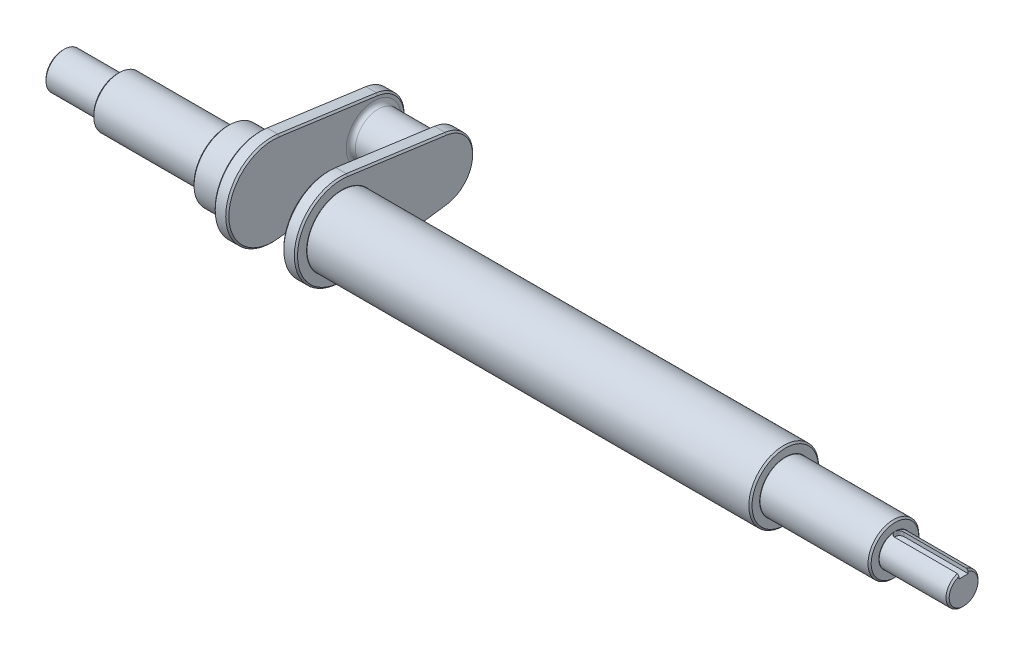
SolidWorks part; units mm, degrees
material "AISI 347 Annealed Stainless Steel (SS)"
ref_plane "Front Plane" through (0, 0, 0) normal (0, 0, 1) x (1, 0, 0)
ref_plane "Top Plane" through (0, 0, 0) normal (0, 1, 0) x (1, 0, 0)
ref_plane "Right Plane" through (0, 0, 0) normal (1, 0, 0) x (0, 0, -1)
ref_plane "R-JPlane" through (30, 0, 0) normal (1, 0, 0) x (0, 0, -1)
ref_plane "L-JPlane" through (-30, 0, 0) normal (1, 0, 0) x (0, 0, -1)
sketch "Sketch1" plane through (-30, 0, 0) normal (1, 0, 0) x (0, 0, -1)
  circle A0 centre (0, 0) radius 38.1
  dimension "D1" = 76.2
extrude "Left-Shaft" add sketch "Sketch1" against normal blind 50
sketch "Sketch2" plane through (30, 0, 0) normal (1, 0, 0) x (0, 0, -1)
  circle A0 centre (0, 0) radius 38.1
  dimension "D1" = 76.2
extrude "Right-Shaft" add sketch "Sketch2" along normal blind 500 separate body
sketch "Sketch5" plane through (-30, 0, 0) normal (1, 0, 0) x (0, 0, -1)
  line L0 (6.8182, 49.5329) -> (114.7727, 34.6731)
  line L1 (6.8182, -49.5329) -> (114.7727, -34.6731)
  arc A0 (6.8182, 49.5329) -> (6.8182, -49.5329) centre (0, 0) ccw
  arc A1 (114.7727, -34.6731) -> (114.7727, 34.6731) centre (110, 0) ccw
  dimension "D1" = 100
  dimension "D2" = 70
  dimension "D3" = 110
extrude "L-Crank" add sketch "Sketch5" against normal blind 15
sketch "Sketch6" plane through (30, 0, 0) normal (1, 0, 0) x (0, 0, -1)
  line L2 (114.7727, 34.6731) -> (6.8182, 49.5329)
  line L3 (6.8182, -49.5329) -> (114.7727, -34.6731)
  line L4 (114.7727, 34.6731) -> (6.8182, 49.5329)
  line L5 (6.8182, -49.5329) -> (114.7727, -34.6731)
  arc A2 (114.7727, -34.6731) -> (114.7727, 34.6731) centre (110, 0) ccw
  arc A3 (6.8182, 49.5329) -> (6.8182, -49.5329) centre (0, 0) ccw
  arc A4 (114.7727, -34.6731) -> (114.7727, 34.6731) centre (110, 0) ccw
  arc A5 (6.8182, 49.5329) -> (6.8182, -49.5329) centre (0, 0) ccw
  dimension "D1" = 0
extrude "R-Crank" add sketch "Sketch6" along normal blind 15
sketch "Sketch7" plane through (-30, 0, 0) normal (1, 0, 0) x (0, 0, -1)
  circle A0 centre (110, 0) radius 25
  dimension "D1" = 50
extrude "Crank Bearing" add sketch "Sketch7" along direction (1, 0, 0) on the side of the normal up to next (60 mm away)
sketch "Sketch3" plane through (-80, 0, 0) normal (-1, 0, 0) x (0, 0, 1)
  circle A0 centre (0, 0) radius 27.7813
  dimension "D1" = 55.5625
extrude "L_Journal" add sketch "Sketch3" along normal blind 120
sketch "Sketch8" plane through (530, 0, 0) normal (1, 0, 0) x (0, 0, -1)
  circle A0 centre (0, 0) radius 27.7813
  dimension "D1" = 55.5625
extrude "R_Journal" add sketch "Sketch8" along normal blind 120
sketch "Sketch9" plane through (-200, 0, 0) normal (-1, 0, 0) x (0, 0, 1)
  circle A0 centre (0, 0) radius 20
  dimension "D1" = 40
extrude "FlyWheel Shaft" add sketch "Sketch9" along normal blind 60
sketch "Sketch10" plane through (650, 0, 0) normal (1, 0, 0) x (0, 0, -1)
  circle A0 centre (0, 0) radius 17.5
  dimension "D1" = 35
extrude "Gear Shaft" add sketch "Sketch10" along normal blind 75
ref_plane "Keyway PLANE" through (0, 12.5, 0) normal (0, 1, 0) x (1, 0, 0)
sketch "Sketch11" plane through (0, 12.5, 0) normal (0, 1, 0) x (1, 0, 0)
  line L0 (745, 0) -> (655, 0) construction
  line L1 (745, -5) -> (655, -5)
  line L2 (745, 5) -> (655, 5)
  line L3 (725, -17.5) -> (725, 17.5) construction
  arc A0 (745, -5) -> (745, 5) centre (745, 0) ccw
  arc A1 (655, 5) -> (655, -5) centre (655, 0) ccw
  point P3 (700, 0)
  dimension "D2" = 90
  dimension "D1" = 10
  dimension "D3" = 20
extrude "KEYWAY" cut sketch "Sketch11" along normal through all
fillet "Crank Fillets" radius 5 2 edges at (30, 0, -135) (-30, 0, -135)
chamfer "External Chamfers" distance 1.75 angle 45 22 edges at (-45, 0, -145) (-45, 42.103, -60.7955) (-45, -42.103, -60.7955) (-45, 0, 50) (-30, 0, -145) (-30, 42.103, -60.7955) (-30, -42.103, -60.7955) (-30, 0, 50) (30, 0, -145) (30, 42.103, -60.7955) (30, -42.103, -60.7955) (30, 0, 50) (45, 0, -145) (45, 42.103, -60.7955) (45, -42.103, -60.7955) (45, 0, 50) (-260, 0, 20) (-200, 0, 27.7812) (-80, 0, -38.1) (530, 0, -38.1) (650, 0, -27.7812) (725, -17.5, 0)
fillet "Fillet1" radius 0.25 6 edges at (650, 0, -17.5) (530, 0, -27.7812) (45, 0, -38.1) (-45, 0, -38.1) (-80, 0, 27.7812) (-200, 0, 20)
equation "\"D1@Sketch2\"=\"D1@Sketch1\""
